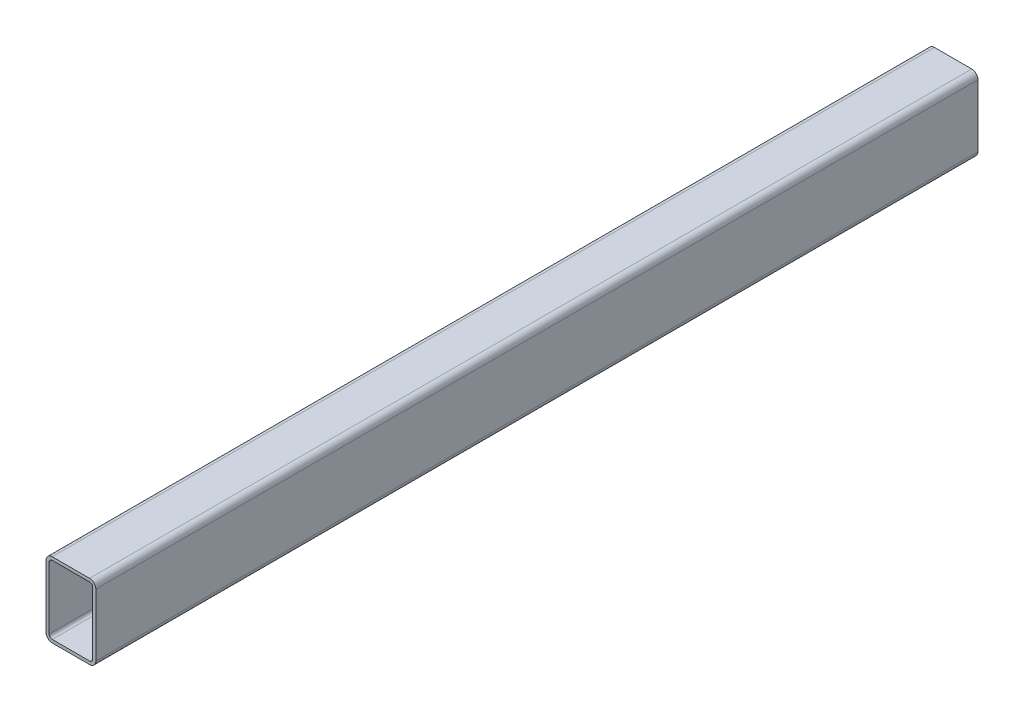
SolidWorks part; units mm, degrees
material "Plain Carbon Steel"
ref_plane "Front Plane" through (0, 0, 0) normal (0, 0, 1) x (1, 0, 0)
ref_plane "Top Plane" through (0, 0, 0) normal (0, 1, 0) x (1, 0, 0)
ref_plane "Right Plane" through (0, 0, 0) normal (1, 0, 0) x (0, 0, -1)
sketch "Sketch13" plane through (0, 0, 0) normal (0, 0, 1) x (1, 0, 0)
  line L4 (19.05, -38.1) -> (-19.05, -38.1)
  line L5 (25.4, 31.75) -> (25.4, -31.75)
  line L6 (-25.4, -31.75) -> (-25.4, 31.75)
  line L7 (-19.05, 38.1) -> (19.05, 38.1)
  line L8 (19.05, -34.925) -> (-19.05, -34.925)
  line L9 (22.225, 31.75) -> (22.225, -31.75)
  line L10 (-19.05, 34.925) -> (19.05, 34.925)
  line L11 (-22.225, -31.75) -> (-22.225, 31.75)
  line L12 (-19.05, 31.75) -> (19.05, -31.75) construction
  line L13 (19.05, 31.75) -> (-19.05, -31.75) construction
  arc A4 (-25.4, -31.75) -> (-19.05, -38.1) centre (-19.05, -31.75) ccw
  arc A5 (19.05, -38.1) -> (25.4, -31.75) centre (19.05, -31.75) ccw
  arc A6 (25.4, 31.75) -> (19.05, 38.1) centre (19.05, 31.75) ccw
  arc A7 (-19.05, 38.1) -> (-25.4, 31.75) centre (-19.05, 31.75) ccw
  arc A8 (-22.225, -31.75) -> (-19.05, -34.925) centre (-19.05, -31.75) ccw
  arc A9 (19.05, -34.925) -> (22.225, -31.75) centre (19.05, -31.75) ccw
  arc A10 (22.225, 31.75) -> (19.05, 34.925) centre (19.05, 31.75) ccw
  arc A11 (-19.05, 34.925) -> (-22.225, 31.75) centre (-19.05, 31.75) ccw
  dimension "D4" = 6.35
  dimension "D2" = 50.8
  dimension "D3" = 76.2
  dimension "D1" = 3.175
extrude "Boss-Extrude2" add sketch "Sketch13" along normal mid plane 899.922 separate body
equation "\"M5_tap\"=4.2mm       ' Below you can do mesurements as follows: cm, mm, ft, in, m, "
equation "\"M5_clearence\"=5.5mm"
equation "\"M6_tap\"=5mm"
equation "\"M6_clearence\"=6.6mm"
